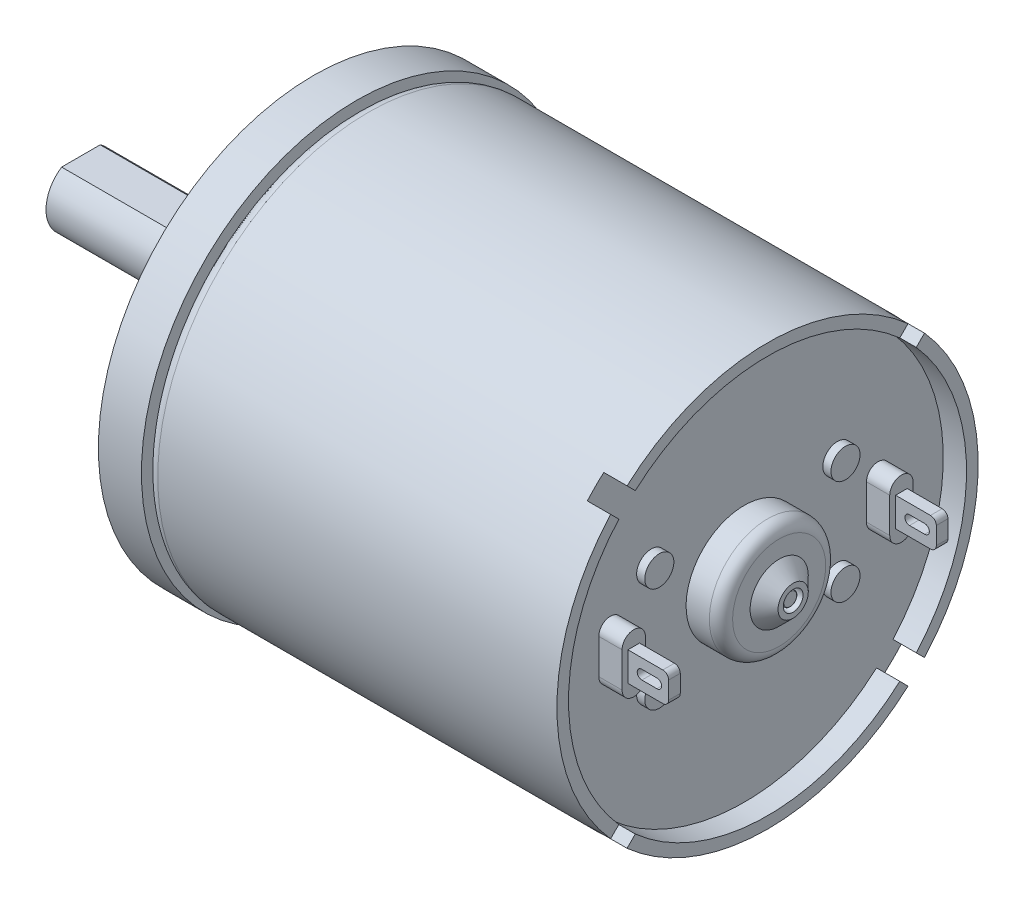
SolidWorks part; units mm, degrees
ref_plane "Alzado" through (0, 0, 0) normal (0, 0, 1) x (1, 0, 0)
ref_plane "Planta" through (0, 0, 0) normal (0, 1, 0) x (1, 0, 0)
ref_plane "Vista lateral" through (0, 0, 0) normal (1, 0, 0) x (0, 0, -1)
sketch "Croquis1" plane through (0, 0, 0) normal (0, 0, 1) x (1, 0, 0)
  line L0 (-50, 0) -> (50, 0) construction
  line L1 (-30.475, 0) -> (-30.475, 3)
  line L2 (-30.475, 3) -> (-15.475, 3)
  line L3 (-15.475, 3) -> (-15.475, 6)
  line L4 (-15.475, 6) -> (-10.475, 6)
  line L5 (-10.475, 6) -> (-10.475, 18.5)
  line L6 (-10.475, 18.5) -> (-6.775, 18.5)
  line L7 (-6.775, 18.5) -> (-6.775, 17.1)
  line L8 (26.525, 18.1) -> (26.525, 5)
  line L9 (26.525, 5) -> (28.525, 5)
  line L10 (29.525, 4) -> (29.525, 2.5)
  line L11 (-5.775, 18.1) -> (26.525, 18.1)
  line L12 (-30.475, 0) -> (30.475, 0)
  line L13 (29.525, 2.5) -> (30.725, 1.3)
  line L14 (29.525, 2.5) -> (31.6999, 2.5) construction
  line L15 (30.725, 1.3) -> (30.725, 0.85)
  line L16 (30.725, 0.85) -> (29.225, 0.85)
  line L17 (29.225, 0.85) -> (29.225, 0.6)
  line L18 (29.225, 0.6) -> (30.425, 0.6)
  line L19 (30.475, 0.55) -> (30.475, 0)
  arc A0 (28.525, 5) -> (29.525, 4) centre (28.525, 4) cw
  arc A2 (-5.775, 18.1) -> (-6.775, 17.1) centre (-5.775, 17.1) ccw
  arc A3 (30.425, 0.6) -> (30.475, 0.55) centre (30.425, 0.55) cw
  point P2 (0, 0)
  point P16 (-5.775, 18.1)
  point P18 (0, 0)
  point P24 (-5.775, 18.1)
  point P26 (-6.775, 17.1)
  point P35 (30.475, 0.6)
  dimension "D12" = 5
  dimension "D8" = 36.2
  dimension "D10" = 1
  dimension "D20" = 2
  dimension "D21" = 0.05
  dimension "D1" = 100
  dimension "D2" = 6
  dimension "D3" = 15
  dimension "D4" = 5
  dimension "D5" = 12
  dimension "D6" = 37
  dimension "D7" = 37
  dimension "D9" = 33.3
  dimension "D11" = 3
  dimension "D13" = 10
  dimension "D14" = 45
  dimension "D15" = 1.2
  dimension "D16" = 1.5
  dimension "D17" = 1.7
  dimension "D18" = 1.2
  dimension "D19" = 1.25
revolve "Revolución1" add sketch "Croquis1" angle 360 about L0
sketch "Croquis3" plane through (26.525, 0, 0) normal (1, 0, 0) x (0, 0, -1)
  line L0 (18.1265, 18.1265) -> (-16.0855, -16.0855) construction
  line L1 (-12.7986, 12.7986) -> (12.7986, -12.7986) construction
  line L2 (0, 12.8224) -> (0, -11.8936) construction
  line L3 (-18.1, 0) -> (18.1, 0) construction
  line L4 (-13.4862, 12.072) -> (-12.7779, 11.3637)
  line L5 (12.072, 13.4862) -> (11.3637, 12.7779)
  line L6 (-12.072, 13.4862) -> (-11.3637, 12.7779)
  line L7 (13.4862, 12.072) -> (12.7779, 11.3637)
  line L8 (-17.5671, 16.1529) -> (14.8371, -16.2513) construction
  line L9 (-16.86, 16.86) -> (15.5442, -15.5442) construction
  line L10 (-16.1529, 17.5671) -> (16.2513, -14.8371) construction
  line L14 (17.4194, 18.8336) -> (-16.7926, -15.3784) construction
  line L16 (18.8336, 17.4194) -> (-15.3784, -16.7926) construction
  line L17 (12.7779, -11.3637) -> (13.4862, -12.072)
  line L18 (11.3637, -12.7779) -> (12.072, -13.4862)
  line L19 (-11.3637, -12.7779) -> (-12.072, -13.4862)
  line L20 (-12.7779, -11.3637) -> (-13.4862, -12.072)
  line L21 (-11.5, 1.5) -> (-11.5, -1.5) construction
  line L22 (-10.5, 1.5) -> (-10.5, -1.5)
  line L23 (-12.5, 1.5) -> (-12.5, -1.5)
  line L24 (11.5, 1.5) -> (11.5, -1.5) construction
  line L25 (10.5, 1.5) -> (10.5, -1.5)
  line L26 (12.5, 1.5) -> (12.5, -1.5)
  arc A0 (-12.7779, 11.3637) -> (-12.7779, -11.3637) centre (0, 0) ccw
  circle A1 centre (0, 0) radius 18.1
  arc A2 (-13.4862, 12.072) -> (-13.4862, -12.072) centre (0, 0) ccw
  circle A3 centre (0, 0) radius 18.1 construction
  circle A4 centre (0, 0) radius 17.1 construction
  arc A5 (12.072, 13.4862) -> (-12.072, 13.4862) centre (0, 0) ccw
  arc A6 (11.3637, 12.7779) -> (-11.3637, 12.7779) centre (0, 0) ccw
  arc A7 (12.7779, -11.3637) -> (12.7779, 11.3637) centre (0, 0) ccw
  arc A8 (13.4862, -12.072) -> (13.4862, 12.072) centre (0, 0) ccw
  arc A9 (-11.3637, -12.7779) -> (11.3637, -12.7779) centre (0, 0) ccw
  arc A10 (-12.072, -13.4862) -> (12.072, -13.4862) centre (0, 0) ccw
  circle A11 centre (0, 0) radius 5 construction
  arc A12 (-10.5, 1.5) -> (-12.5, 1.5) centre (-11.5, 1.5) ccw
  arc A13 (-12.5, -1.5) -> (-10.5, -1.5) centre (-11.5, -1.5) ccw
  arc A14 (10.5, 1.5) -> (12.5, 1.5) centre (11.5, 1.5) cw
  arc A15 (12.5, -1.5) -> (10.5, -1.5) centre (11.5, -1.5) cw
  circle A16 centre (-8, 4.5) radius 1.25
  circle A17 centre (8, 4.5) radius 1.25
  circle A18 centre (8, -4.5) radius 1.25
  circle A19 centre (-8, -4.5) radius 1.25
  point P27 (13.4862, 0)
  point P28 (-5, 0)
  point P31 (-11.5, 0)
  point P47 (-11.5, 0)
  point P52 (8, 4.5)
  point P53 (8, -4.5)
  point P56 (11.5, 0)
  point P61 (-8, 4.5)
  point P62 (-8, -4.5)
  dimension "D14" = 2.5
  dimension "D3" = 90
  dimension "D4" = 45
  dimension "D5" = 1
  dimension "D7" = 6.5
  dimension "D8" = 2
  dimension "D9" = 3
  dimension "D10" = 9
  dimension "D11" = 4.5
  dimension "D12" = 16
  dimension "D13" = 8
  dimension "D1" = 0
  dimension "D2" = 1
  dimension "D6" = 1
extrude "Saliente-Extruir1" add sketch "Croquis3" along normal blind 2 contours A2 L20 A0 L4 | L6 A6 L5 A5 | L7 A7 L17 A8 | A10 L18 A9 L19 | L23 A13 L22 A12 | L25 A15 L26 A14
ref_plane "Plano1" through (0, 0, 11.5) normal (0, 0, 1) x (1, 0, 0)
sketch "Croquis5" plane through (0, 0, 11.5) normal (0, 0, 1) x (1, 0, 0)
  line L0 (28.525, 1.25) -> (31.525, 1.25)
  line L1 (28.525, -12.072) -> (28.525, 12.072) construction
  line L2 (32.025, 0.75) -> (32.025, -0.75)
  line L3 (31.525, -1.25) -> (28.525, -1.25)
  line L4 (28.525, -1.25) -> (28.525, 1.25)
  line L5 (28.525, 0) -> (43.1516, 0) construction
  line L6 (29.725, 0) -> (31.025, 0) construction
  line L7 (29.725, 0.4) -> (31.025, 0.4)
  line L8 (29.725, -0.4) -> (31.025, -0.4)
  arc A0 (32.025, -0.75) -> (31.525, -1.25) centre (31.525, -0.75) cw
  arc A1 (31.525, 1.25) -> (32.025, 0.75) centre (31.525, 0.75) cw
  arc A2 (29.725, 0.4) -> (29.725, -0.4) centre (29.725, 0) ccw
  arc A3 (31.025, -0.4) -> (31.025, 0.4) centre (31.025, 0) ccw
  point P15 (30.375, 0)
  dimension "D3" = 0.5
  dimension "D6" = 1.3
  dimension "D7" = 1
  dimension "D1" = 2.5
  dimension "D2" = 1.25
  dimension "D4" = 3.5
  dimension "D5" = 0.8
extrude "Saliente-Extruir2" add sketch "Croquis5" along normal mid plane 1
mirror "Simetría1" about plane through (0, 0, 0) normal (0, 0, 1) of "Saliente-Extruir2"
extrude "Saliente-Extruir3" add sketch "Croquis3<5>" along normal blind 0.7 separate body contours A16 | A17 | A18 | A19 region at (26.525, 4.5, 8) region at (26.525, 4.5, -8) region at (26.525, -4.5, -8) region at (26.525, -4.5, 8)
sketch "Croquis3<5>" plane through (26.525, 0, 0) normal (1, 0, 0) x (0, 0, -1) same geometry as "Croquis3"
sketch "Croquis7" plane through (-30.475, 0, 0) normal (-1, 0, 0) x (0, 0, 1)
  line L1 (-1.6583, 2.5) -> (1.6583, 2.5)
  circle A0 centre (0, 0) radius 3 construction
  circle A1 centre (0, 0) radius 3 construction
  circle A3 centre (0, 0) radius 3
  arc A5 (1.6583, 2.5) -> (-1.6583, 2.5) centre (0, 0) ccw
  point P6 (0, -3)
  dimension "D2" = 5.5
  dimension "D3" = 3.3166
  dimension "D1" = 0
extrude "Cortar-Extruir1" cut sketch "Croquis7" against normal blind 14
hole_wizard "Taladro roscado M3x0.51" positions "Croquis8" profile "Croquis10" tap size "M3x0.5" standard "Ansi Metric"
sketch "Croquis8" plane through (-10.475, 0, 0) normal (-1, 0, 0) x (0, 0, 1)
  circle A0 centre (0, 0) radius 15.5 construction
  point P0 (0, 15.5)
  point P21 (13.4234, 7.75)
  point P22 (13.4234, -7.75)
  point P23 (0, -15.5)
  point P24 (-13.4234, -7.75)
  point P25 (-13.4234, 7.75)
  dimension "D1" = 31
  dimension "D2" = 6
cosmetic thread "Rosca de taladro1" parameters "D1"=5, "D2"=3
cosmetic thread "Rosca de taladro2" parameters "D1"=5, "D2"=3
cosmetic thread "Rosca de taladro3" parameters "D1"=5, "D2"=3
cosmetic thread "Rosca de taladro4" parameters "D1"=5, "D2"=3
cosmetic thread "Rosca de taladro5" parameters "D1"=5, "D2"=3
cosmetic thread "Rosca de taladro6" parameters "D1"=5, "D2"=3
sketch "Croquis10" plane through (-10.475, 15.5, 0) normal (0, 1, 0) x (0, 0, 1)
  line L0 (0, 0) -> (0, 5.7511)
  line L1 (0, 5.7511) -> (1.25, 5)
  line L2 (1.25, 5) -> (1.25, 0.3164)
  line L3 (1.25, 0.3164) -> (1.525, 0)
  line L5 (1.525, 0) -> (0, 0)
  line L6 (-1.25, 0.3164) -> (-1.525, 0) construction
  line L10 (0, 5.7511) -> (-1.25, 5) construction
  line L11 (0, -6.35) -> (0, 107.95) construction
  dimension "Diámetro de perforador para roscar" = 2.5
  dimension "Profundidad de perforador para roscar" = 5
  dimension "Diámetro de avellanado cercano" = 3.05
  dimension "Ángulo de avellanado cercano" = 82
  dimension "Ángulo de perforador" = 118
sketch "Croquis11" plane through (-10.475, 0, 0) normal (-1, 0, 0) x (0, 0, 1)
  line L0 (-18.5, 0) -> (18.5, 0) construction
  line L1 (11.2583, 6.5) -> (-18.8285, -10.8706) construction
  line L2 (-13.4234, 7.75) -> (22.0947, -12.7564) construction
  line L3 (0, 18.5) -> (0, -18.5) construction
  line L4 (-10.6747, 5.2393) -> (-7.5943, 3.4608)
  line L5 (-0.8, 11.8642) -> (-0.8, 8.3072)
  line L6 (9.8747, 6.6249) -> (6.7943, 4.8464)
  line L8 (-9.8747, 6.6249) -> (-6.7943, 4.8464)
  line L9 (0.8, 11.8642) -> (0.8, 8.3072)
  line L10 (10.6747, 5.2393) -> (7.5943, 3.4608)
  line L12 (-20.8102, 12.9385) -> (22.4947, -12.0636) construction
  line L13 (-21.2102, 12.2457) -> (22.0947, -12.7564) construction
  line L14 (-21.6102, 11.5529) -> (21.6947, -13.4492) construction
  line L15 (18.5401, 11.6279) -> (-19.2285, -10.1778) construction
  line L16 (18.9401, 10.935) -> (-18.8285, -10.8706) construction
  line L17 (19.3401, 10.2422) -> (-18.4285, -11.5634) construction
  line L18 (-0.8, 18.5) -> (-0.8, -18.5) construction
  line L19 (0.8, 18.5) -> (0.8, -18.5) construction
  line L22 (-0.8, -8.3072) -> (-0.8, -11.8642)
  line L23 (0.8, -8.3072) -> (0.8, -11.8642)
  line L24 (6.7943, -4.8464) -> (9.8747, -6.6249)
  line L25 (-6.7943, -4.8464) -> (-9.8747, -6.6249)
  line L26 (-7.5943, -3.4608) -> (-10.6747, -5.2393)
  line L27 (7.5943, -3.4608) -> (10.6747, -5.2393)
  arc A0 (-7.142, 2.2895) -> (-7.142, -2.2895) centre (0, 0) ccw
  arc A1 (-12.106, 4.7377) -> (-12.106, -4.7377) centre (0, 0) ccw
  circle A2 centre (0, 0) radius 18.5 construction
  arc A3 (10.156, 8.1152) -> (1.95, 12.8529) centre (0, 0) ccw
  arc A4 (5.5538, 5.0404) -> (1.5882, 7.3299) centre (0, 0) ccw
  arc A5 (-1.95, 12.8529) -> (-10.156, 8.1152) centre (0, 0) ccw
  arc A6 (-1.5882, 7.3299) -> (-5.5538, 5.0404) centre (0, 0) ccw
  arc A7 (12.106, -4.7377) -> (12.106, 4.7377) centre (0, 0) ccw
  arc A8 (-10.156, -8.1152) -> (-1.95, -12.8529) centre (0, 0) ccw
  arc A9 (-5.5538, -5.0404) -> (-1.5882, -7.3299) centre (0, 0) ccw
  arc A10 (1.5882, -7.3299) -> (5.5538, -5.0404) centre (0, 0) ccw
  arc A11 (1.95, -12.8529) -> (10.156, -8.1152) centre (0, 0) ccw
  arc A12 (7.142, -2.2895) -> (7.142, 2.2895) centre (0, 0) ccw
  arc A13 (-9.8747, -6.6249) -> (-10.156, -8.1152) centre (-9.3747, -7.491) ccw
  arc A14 (-5.5538, -5.0404) -> (-6.7943, -4.8464) centre (-6.2943, -5.7125) ccw
  arc A15 (-0.8, -8.3072) -> (-1.5882, -7.3299) centre (-1.8, -8.3072) ccw
  arc A16 (-1.95, -12.8529) -> (-0.8, -11.8642) centre (-1.8, -11.8642) ccw
  arc A17 (1.95, -12.8529) -> (0.8, -11.8642) centre (1.8, -11.8642) cw
  arc A18 (0.8, -8.3072) -> (1.5882, -7.3299) centre (1.8, -8.3072) cw
  arc A19 (6.7943, -4.8464) -> (5.5538, -5.0404) centre (6.2943, -5.7125) ccw
  arc A20 (9.8747, -6.6249) -> (10.156, -8.1152) centre (9.3747, -7.491) cw
  arc A21 (10.6747, -5.2393) -> (12.106, -4.7377) centre (11.1747, -4.3733) ccw
  arc A22 (7.142, -2.2895) -> (7.5943, -3.4608) centre (8.0943, -2.5948) ccw
  arc A23 (7.5943, 3.4608) -> (7.142, 2.2895) centre (8.0943, 2.5948) ccw
  arc A24 (10.6747, 5.2393) -> (12.106, 4.7377) centre (11.1747, 4.3733) cw
  arc A25 (9.8747, 6.6249) -> (10.156, 8.1152) centre (9.3747, 7.491) ccw
  arc A26 (5.5538, 5.0404) -> (6.7943, 4.8464) centre (6.2943, 5.7125) ccw
  arc A27 (1.5882, 7.3299) -> (0.8, 8.3072) centre (1.8, 8.3072) cw
  arc A28 (1.95, 12.8529) -> (0.8, 11.8642) centre (1.8, 11.8642) ccw
  arc A29 (-1.95, 12.8529) -> (-0.8, 11.8642) centre (-1.8, 11.8642) cw
  arc A30 (-1.5882, 7.3299) -> (-0.8, 8.3072) centre (-1.8, 8.3072) ccw
  arc A31 (-5.5538, 5.0404) -> (-6.7943, 4.8464) centre (-6.2943, 5.7125) cw
  arc A32 (-9.8747, 6.6249) -> (-10.156, 8.1152) centre (-9.3747, 7.491) cw
  arc A33 (-10.6747, -5.2393) -> (-12.106, -4.7377) centre (-11.1747, -4.3733) cw
  arc A34 (-7.142, -2.2895) -> (-7.5943, -3.4608) centre (-8.0943, -2.5948) cw
  arc A35 (-7.142, 2.2895) -> (-7.5943, 3.4608) centre (-8.0943, 2.5948) ccw
  arc A36 (-10.6747, 5.2393) -> (-12.106, 4.7377) centre (-11.1747, 4.3733) ccw
  point P15 (13.4234, 7.75)
  point P16 (-13.4234, 7.75)
  point P33 (-10.837, -7.1805)
  point P54 (-6.0581, -4.4214)
  point P71 (0.8, -7.4572)
  point P74 (6.0581, -4.4214)
  point P79 (11.637, -5.7949)
  point P82 (6.8581, -3.0358)
  point P89 (10.837, 7.1805)
  point P108 (-6.8581, -3.0358)
  dimension "D1" = 26
  dimension "D2" = 15
  dimension "D5" = 1
  dimension "D3" = 0.8
  dimension "D4" = 0.8
extrude "Cortar-Extruir2" cut sketch "Croquis11" against normal blind 0.2
